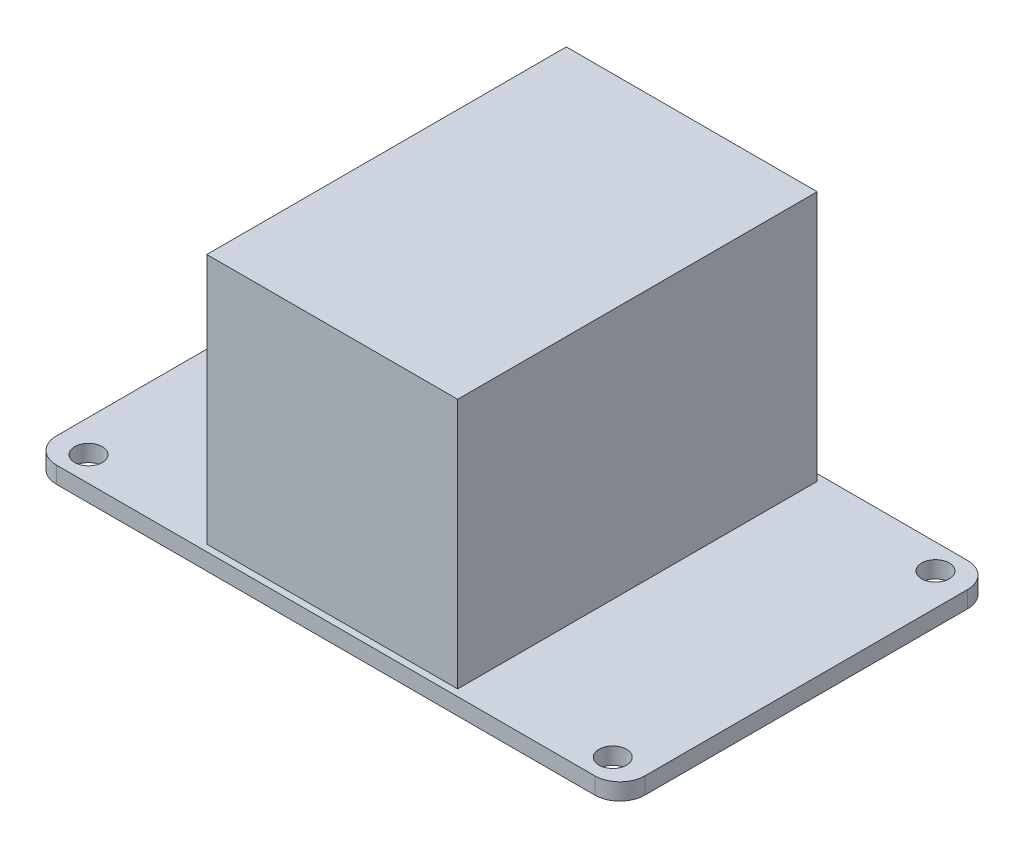
SolidWorks part; units mm, degrees
ref_plane "Front Plane" through (0, 0, 0) normal (0, 0, 1) x (1, 0, 0)
ref_plane "Top Plane" through (0, 0, 0) normal (0, 1, 0) x (1, 0, 0)
ref_plane "Right Plane" through (0, 0, 0) normal (1, 0, 0) x (0, 0, -1)
sketch "Sketch1" plane through (0, 0, 0) normal (0, 1, 0) x (1, 0, 0)
  line L1 (-35.2, -22.3) -> (35.2, -22.3)
  line L2 (-35.2, -22.3) -> (-35.2, 22.3)
  line L3 (-35.2, 22.3) -> (35.2, 22.3)
  line L4 (35.2, -22.3) -> (35.2, 22.3)
  line L5 (-35.2, -22.3) -> (35.2, 22.3) construction
  line L6 (-35.2, 22.3) -> (35.2, -22.3) construction
  point P0 (0, 0)
  dimension "D1" = 44.6
  dimension "D2" = 70.4
extrude "Boss-Extrude1" add sketch "Sketch1" along normal blind 2
sketch "Sketch3" plane through (0, 2, 0) normal (0, 1, 0) x (1, 0, 0)
  line L0 (-31.35, 19.3) -> (31.35, -19.3) construction
  line L1 (31.35, 19.3) -> (-31.35, -19.3) construction
  line L12 (31.35, -19.3) -> (31.35, 19.3) construction
  line L13 (31.35, 19.3) -> (-31.35, 19.3) construction
  line L14 (-31.35, 19.3) -> (-31.35, -19.3) construction
  line L15 (-31.35, -19.3) -> (31.35, -19.3) construction
  circle A0 centre (-31.35, 19.3) radius 1.65
  circle A1 centre (31.35, 19.3) radius 1.65
  circle A2 centre (31.35, -19.3) radius 1.65
  circle A3 centre (-31.35, -19.3) radius 1.65
  point P4 (-33, 19.3)
  point P5 (33, 19.3)
  point P7 (0, 0)
  dimension "D2" = 3.3
  dimension "D1" = 66
extrude "Cut-Extrude1" cut sketch "Sketch3" against normal through all
fillet "Fillet1" radius 3 4 edges at (35.2, 1, -22.3) (35.2, 1, 22.3) (-35.2, 1, -22.3) (-35.2, 1, 22.3)
sketch "Sketch4" plane through (0, 2, 0) normal (0, 1, 0) x (1, 0, 0)
  line L1 (-15, -21.5) -> (15, -21.5)
  line L2 (-15, -21.5) -> (-15, 21.5)
  line L3 (-15, 21.5) -> (15, 21.5)
  line L4 (15, -21.5) -> (15, 21.5)
  line L5 (-15, -21.5) -> (15, 21.5) construction
  line L6 (-15, 21.5) -> (15, -21.5) construction
  point P0 (0, 0)
  dimension "D1" = 30
  dimension "D2" = 43
extrude "Boss-Extrude2" add sketch "Sketch4" along normal blind 30
